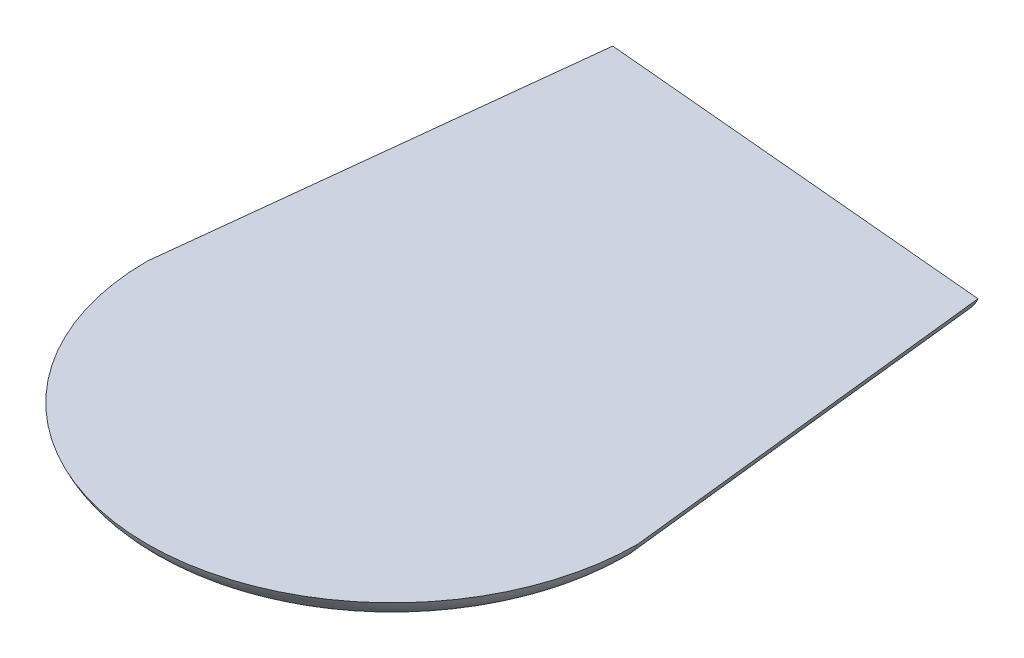
SolidWorks part; units mm, degrees
ref_plane "Front Plane" through (0, 0, 0) normal (0, 0, 1) x (1, 0, 0)
ref_plane "Top Plane" through (0, 0, 0) normal (0, 1, 0) x (1, 0, 0)
ref_plane "Right Plane" through (0, 0, 0) normal (1, 0, 0) x (0, 0, -1)
sketch "Sketch1" plane through (0, 0, 0) normal (0, 1, 0) x (1, 0, 0)
  line L0 (-68.7161, 28.1705) -> (-69.4925, 21.1705)
  line L1 (-21.7208, 49.3214) -> (-65.9278, 53.3078)
  line L2 (-65.9278, 53.3078) -> (-68.7161, 28.1705)
  line L3 (-68.7161, 28.1705) -> (-32.0454, 28.1705)
  line L4 (-32.0454, 28.1705) -> (-32.0454, -2.0922)
  line L5 (-32.0454, -2.0922) -> (-56.0454, -2.0922)
  line L6 (-56.0454, -2.0922) -> (-56.0454, 21.1705)
  line L7 (-56.0454, 21.1705) -> (-69.4925, 21.1705)
  line L8 (-69.4925, 21.1705) -> (-71.0454, 7.1705)
  line L9 (-17.0454, 7.1705) -> (-21.7208, 49.3214)
  arc A0 (-71.0454, 7.1705) -> (-17.0454, 7.1705) centre (-44.0454, 7.1705) ccw
extrude "Boss-Extrude1" add sketch "Sketch1" along normal blind 3 contours L8 A0 L9 L1 L2 L3 L4 L5 L6 L7 | L7 L6 L5 L4 L3 L0 region at (-46.117, 0, -14.3355) region at (-66.4184, 0, -40.6389)
fillet "Fillet1" radius 5 3 edges at (-19.3831, 3, -28.2459) (-68.4866, 3, -30.2391) (-44.0454, 3, 19.8295)
mirror "Mirror1" about plane through (0, 0, 0) normal (0, 1, 0) of bodies 101
delete or keep bodies "Body-Delete/Keep 1" type delete bodies bodies 101
